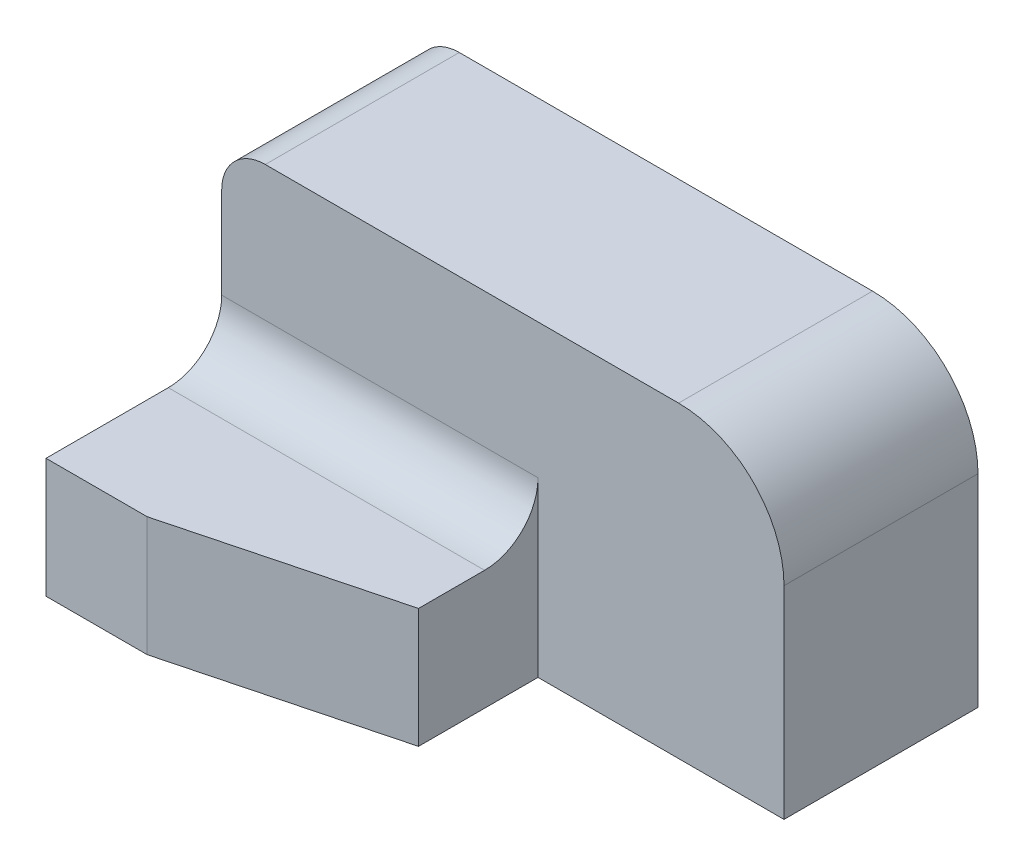
SolidWorks part; units mm, degrees
ref_plane "Front Plane" through (0, 0, 0) normal (0, 0, 1) x (1, 0, 0)
ref_plane "Top Plane" through (0, 0, 0) normal (0, 1, 0) x (1, 0, 0)
ref_plane "Right Plane" through (0, 0, 0) normal (1, 0, 0) x (0, 0, -1)
sketch "Sketch1" plane through (0, 0, 0) normal (0, 0, 1) x (1, 0, 0)
  line L1 (0, 0) -> (-101.6, 0)
  line L2 (0, 0) -> (0, 36.576)
  line L3 (-19.05, 55.626) -> (-93.726, 55.626)
  line L4 (-101.6, 0) -> (-101.6, 47.752)
  line L5 (-101.6, 0) -> (-44.45, 0)
  line L6 (-101.6, 0) -> (-101.6, 21.59)
  line L7 (-101.6, 21.59) -> (-44.45, 21.59)
  line L8 (-44.45, 0) -> (-44.45, 21.59)
  arc A0 (0, 36.576) -> (-19.05, 55.626) centre (-19.05, 36.576) ccw
  arc A1 (-101.6, 47.752) -> (-93.726, 55.626) centre (-93.726, 47.752) cw
  point P7 (0, 55.626)
  point P10 (-101.6, 55.626)
  dimension "D3" = 19.05
  dimension "D4" = 7.874
  dimension "D1" = 55.626
  dimension "D2" = 101.6
  dimension "D5" = 57.15
  dimension "D6" = 21.59
extrude "Boss-Extrude1" add sketch "Sketch1" along normal blind 35.052 contours A1 L4 L7 L8 L1 L2 A0 L3 | L1 L8 L7 L4 region at (-45.1488, 32.1621, 0) region at (-73.025, 10.795, 0)
extrude "Boss-Extrude2" add sketch "Sketch1<4>" along normal blind 66.802 contours L1 L8 L7 L4 region at (-73.025, 10.795, 0)
sketch "Sketch1<4>" plane through (0, 0, 0) normal (0, 0, 1) x (1, 0, 0) same geometry as "Sketch1"
fillet "Fillet1" radius 9.652 1 edges at (-73.025, 21.59, 35.052)
sketch "Sketch3" plane through (0, 21.59, 0) normal (0, 1, 0) x (1, 0, 0)
  line L0 (-83.312, -66.802) -> (-44.45, -56.642)
  line L1 (-101.6, -66.802) -> (-44.45, -66.802) construction
  line L2 (-44.45, -66.802) -> (-44.45, -44.704) construction
  line L3 (-83.312, -66.802) -> (-44.45, -66.802)
  line L4 (-44.45, -66.802) -> (-44.45, -56.642)
  dimension "D1" = 10.16
  dimension "D2" = 38.862
extrude "Cut-Extrude1" cut sketch "Sketch3" against normal through all
